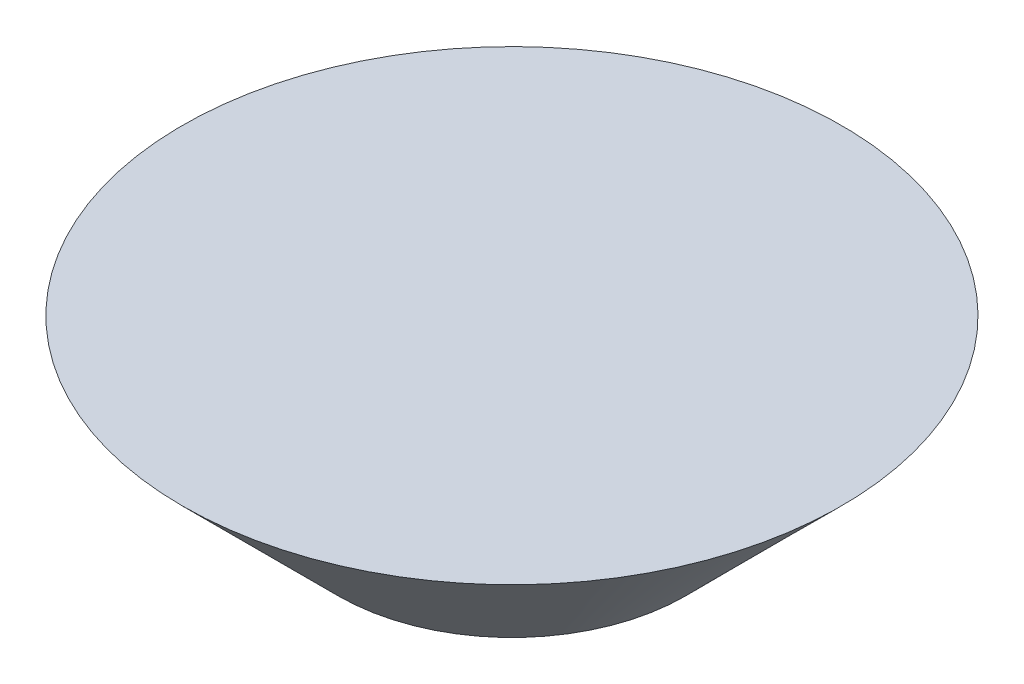
SolidWorks part; units mm, degrees
ref_plane "Płaszczyzna przednia" through (0, 0, 0) normal (0, 0, 1) x (1, 0, 0)
ref_plane "Płaszczyzna górna" through (0, 0, 0) normal (0, 1, 0) x (1, 0, 0)
ref_plane "Płaszczyzna prawa" through (0, 0, 0) normal (1, 0, 0) x (0, 0, -1)
sketch "Szkic1" plane through (0, 0, 0) normal (0, 1, 0) x (1, 0, 0)
  circle A0 centre (0, 0) radius 76
  dimension "D1" = 152
extrude "Dodanie-wyciągnięcie1" add sketch "Szkic1" along normal blind 36
chamfer "Sfazowanie1" distance 36 angle 45 1 edges at (0, 0, 76)
